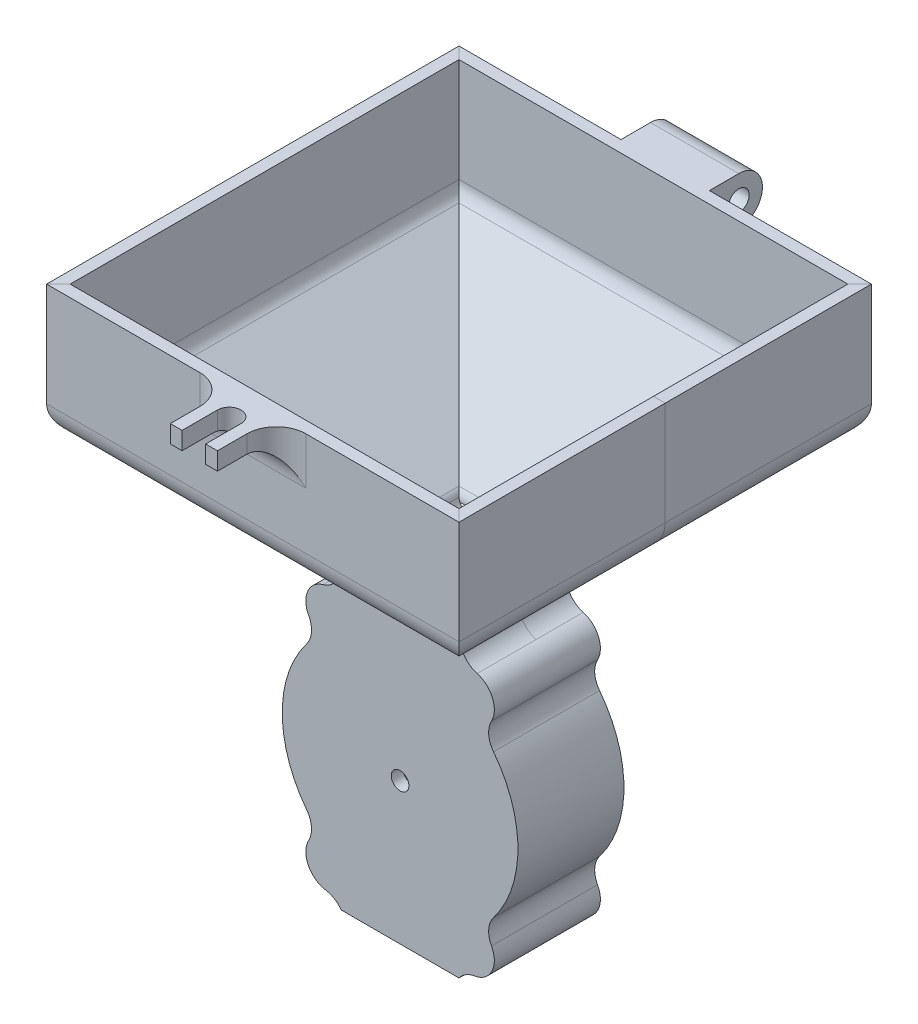
SolidWorks part; units mm, degrees
material "PP Copolymer"
ref_plane "Alzado" through (0, 0, 0) normal (0, 0, 1) x (1, 0, 0)
ref_plane "Planta" through (0, 0, 0) normal (0, 1, 0) x (1, 0, 0)
ref_plane "Vista lateral" through (0, 0, 0) normal (1, 0, 0) x (0, 0, -1)
sketch "Croquis1" plane through (0, 0, 0) normal (0, 0, 1) x (1, 0, 0)
  line L1 (0, 0) -> (0, 20) construction
  circle A0 centre (0, 0) radius 20
  dimension "D1" = 40
extrude "Saliente-Extruir1" add sketch "Croquis1" along normal mid plane 20
sketch "Croquis2" plane through (0, 0, 0) normal (0, 1, 0) x (1, 0, 0)
  line L1 (10, -10) -> (-10, -10)
  line L2 (10, -10) -> (10, 10)
  line L3 (10, 10) -> (-10, 10)
  line L4 (-10, -10) -> (-10, 10)
  line L5 (10, -10) -> (-10, 10) construction
  line L6 (10, 10) -> (-10, -10) construction
  dimension "D1" = 20
extrude "Saliente-Extruir2" add sketch "Croquis2" against normal blind 24
sketch "Croquis4" plane through (0, 0, 0) normal (0, 1, 0) x (1, 0, 0)
  line L1 (10, -10) -> (-10, -10)
  line L2 (10, -10) -> (10, 10)
  line L3 (10, 10) -> (-10, 10)
  line L4 (-10, -10) -> (-10, 10)
  line L5 (10, -10) -> (-10, 10) construction
  line L6 (10, 10) -> (-10, -10) construction
  line L7 (20, 10) -> (-20, 10) construction
  point P0 (0, 0)
extrude "Saliente-Extruir3" add sketch "Croquis4" along normal blind 28
shell "Vaciado1" thickness 2 removed face at (0, -24, 0) removed face at (0, 28, 0)
fillet "Redondeo1" radius 5 2 edges at (8, -16.1245, 0) (-8, -16.1245, 0)
sketch "Croquis6" plane through (0, 0, -10) normal (0, 0, -1) x (-1, 0, 0)
  line L6 (10, 17.3205) -> (10, 28)
  line L7 (10, 28) -> (-10, 28)
  line L8 (-10, 28) -> (-10, 17.3205)
  line L9 (10, 17.3205) -> (10, 28) construction
  line L10 (10, 28) -> (-10, 28) construction
  line L11 (-10, 28) -> (-10, 17.3205) construction
  line L12 (-10, -17.3205) -> (-10, -24)
  line L13 (-10, -17.3205) -> (-10, -24)
  line L14 (-10, -24) -> (10, -24)
  line L15 (-10, -24) -> (10, -24)
  line L16 (10, -24) -> (10, -17.3205)
  line L17 (10, -24) -> (10, -17.3205)
  arc A4 (10, -17.3205) -> (10, 17.3205) centre (0, 0) ccw
  arc A5 (-10, 17.3205) -> (-10, -17.3205) centre (0, 0) ccw
  arc A6 (10, -17.3205) -> (10, 17.3205) centre (0, 0) ccw construction
  arc A7 (-10, 17.3205) -> (-10, -17.3205) centre (0, 0) ccw construction
  dimension "D1" = 0
extrude "Cortar-Extruir2" cut sketch "Croquis6" against normal blind 2 contours A5 L6 L7 L8 A4 region at (0, 1.3583, -10)
sketch "Croquis7" plane through (0, 0, 8) normal (0, 0, -1) x (-1, 0, 0)
  line L0 (8, 28) -> (-0.2973, 19.7027)
  line L3 (8, 28) -> (-8, 28) construction
  line L4 (8, 28) -> (8, 16.1245)
  arc A0 (8, 16.1245) -> (0.3882, 17.9958) centre (0, 0) ccw
  arc A1 (-0.2973, 19.7027) -> (0.3882, 17.9958) centre (0.4098, 18.9956) ccw
  dimension "D3" = 2
  dimension "D2" = 45
extrude "Saliente-Extruir4" add sketch "Croquis7" along normal up to surface (16 mm away) up to face at (-11.1703, -0.9785, -8)
fillet "Redondeo2" radius 5 1 edges at (8, 16.1245, 0)
fillet "Redondeo3" radius 2 4 edges at (-10, 17.3205, 1) (-10, -17.3205, 1) (10, -17.3205, 1) (10, 17.3205, 1)
sketch "Croquis10" plane through (0, 0, 0) normal (0, 0, 1) x (1, 0, 0)
  line L0 (8, 28) -> (8, 28.9612)
  line L1 (8, 28.9612) -> (33, 48.9612)
  line L2 (10, 28) -> (35, 48)
  line L3 (8, 28) -> (10, 28) construction
  line L4 (35, 48) -> (35, 68)
  line L5 (33, 48.9612) -> (33, 68)
  line L6 (33, 68) -> (35, 68)
  line L7 (-8, 28) -> (8, 28) construction
  line L8 (8, 28) -> (10, 28)
  line L11 (0, 0) -> (0, 28) construction
  dimension "D1" = 2
  dimension "D2" = 20
  dimension "D3" = 40
  dimension "D4" = 35
  dimension "D5" = 38.66
sketch "Croquis11" plane through (0, 28, 0) normal (0, 1, 0) x (1, 0, 0)
  line L1 (-10, 10) -> (10, 10)
  line L2 (-10, 10) -> (-10, -10)
  line L3 (-10, -10) -> (10, -10)
  line L4 (10, 10) -> (10, -10)
  line L5 (-10, 10) -> (10, -10) construction
  line L6 (-10, -10) -> (10, 10) construction
  point P0 (0, 0)
sweep "Barrer2" add profiles "Croquis10" path "Croquis11"
fillet "Redondeo4" radius 2 5 edges at (8, 28.9612, -4) (0, 28.9612, -8) (8, 28.9612, 4) (-8, 28.9612, 0) (0, 28.9612, 8)
fillet "Redondeo5" radius 5 9 edges at (35, 48, 17.5) (10, 28, -4) (-35, 48, 0) (0, 48, -35) (0, 48, 35) (35, 48, -17.5) (10, 28, 5) (0, 28, 10) (-10, 28, 1)
fillet "Redondeo6" radius 3 6 edges at (33, 48.9612, 16.5) (0, 48.9612, -33) (-33, 48.9612, 0) (0, 48.9612, 33) (33, 48.9612, -16.5) (-8, 28, 0)
sketch "Croquis12" plane through (0, 0, 10) normal (0, 0, 1) x (1, 0, 0)
  circle A0 centre (0, 0) radius 1.5
  dimension "D1" = 3
extrude "Cortar-Extruir3" cut sketch "Croquis12" against normal blind 2
sketch "Croquis13" plane through (0, 68, 0) normal (0, 1, 0) x (1, 0, 0)
  line L0 (35, -35) -> (-35, -35) construction
  line L1 (4, -45) -> (2, -45)
  line L2 (4, -45) -> (4, -35)
  line L3 (4, -35) -> (-4, -35)
  line L4 (-4, -45) -> (-4, -35)
  line L5 (4, -45) -> (-4, -35) construction
  line L6 (4, -35) -> (-4, -45) construction
  line L7 (-2, -39) -> (-2, -45)
  line L8 (2, -39) -> (2, -45)
  line L9 (-2, -45) -> (-4, -45)
  arc A0 (2, -39) -> (-2, -39) centre (0, -39) ccw
  point P0 (0, -40)
  dimension "D3" = 2
  dimension "D1" = 10
  dimension "D2" = 8
  dimension "D4" = 1
extrude "Saliente-Extruir5" add sketch "Croquis13" against normal blind 3
fillet "Redondeo7" radius 5 2 edges at (-4, 66.5, 35) (4, 66.5, 35)
fillet "Redondeo8" radius 5 1 edges at (0, 65, 35)
sketch "Croquis14" plane through (0, 0, -8) normal (0, 0, -1) x (-1, 0, 0)
  line L0 (0, 0) -> (0, 28) construction
  line L1 (7.8385, 28) -> (-8, 28) construction
  line L4 (-10, -21.9032) -> (-10, -18.4391)
  line L5 (-10.9091, -16.7628) -> (-13.5192, -14.7388)
  line L6 (-10.9091, 16.7628) -> (-13.5192, 14.7388)
  line L7 (-10, 18.4391) -> (-10, 21.9032)
  line L10 (10, -21.9032) -> (10, -18.4391)
  line L19 (8, -18.9737) -> (8, -24)
  line L20 (8, -24) -> (10, -24)
  line L21 (10, -24) -> (10, -18.4391)
  line L22 (10, 18.4391) -> (10, 25.5969)
  line L23 (11.8765, 29.5012) -> (10, 28)
  line L24 (10, 28) -> (8, 28)
  line L25 (8, 28) -> (7.8385, 28)
  line L26 (7.3395, 27.3395) -> (-0.2973, 19.7027)
  line L29 (10, -21.9032) -> (10, -18.4391)
  line L30 (10, 18.4391) -> (10, 21.9032)
  circle A0 centre (-12, 18.4391) radius 2 construction
  arc A1 (-10, 21.9032) -> (-13.5192, 14.7388) centre (-12, 18.4391) ccw
  circle A2 centre (-12, -18.4391) radius 2 construction
  arc A3 (-13.5192, -14.7388) -> (-10, -21.9032) centre (-12, -18.4391) ccw
  arc A8 (-10.9091, 16.7628) -> (-10.9091, -16.7628) centre (0, 0) ccw construction
  circle A10 centre (12, -18.4391) radius 2 construction
  arc A11 (10, -21.9032) -> (13.5192, -14.7388) centre (12, -18.4391) ccw
  circle A13 centre (12, 18.4391) radius 2 construction
  arc A14 (13.5192, 14.7388) -> (10, 21.9032) centre (12, 18.4391) ccw
  arc A15 (10.9091, -16.7628) -> (10.9091, 16.7628) centre (0, 0) ccw construction
  arc A16 (10.9091, -16.7628) -> (13.5192, -14.7388) centre (0, 0) ccw
  arc A17 (13.5192, 14.7388) -> (10.9091, 16.7628) centre (0, 0) ccw
  arc A18 (-10.9091, -16.7628) -> (-10, -18.4391) centre (-12, -18.4391) cw
  arc A19 (10, -18.4391) -> (10.9091, -16.7628) centre (12, -18.4391) cw
  arc A20 (10, 18.4391) -> (10.9091, 16.7628) centre (12, 18.4391) ccw
  arc A21 (10.1739, -14.849) -> (0.3882, 17.9958) centre (0, 0) ccw
  arc A22 (10.1739, -14.849) -> (8, -18.9737) centre (13, -18.9737) ccw
  arc A23 (10.9091, -16.7628) -> (10, -18.4391) centre (12, -18.4391) ccw
  arc A24 (10.9091, -16.7628) -> (10.9091, 16.7628) centre (0, 0) ccw
  arc A25 (10, 18.4391) -> (10.9091, 16.7628) centre (12, 18.4391) ccw
  arc A26 (11.8765, 29.5012) -> (10, 25.5969) centre (15, 25.5969) ccw
  arc A27 (7.3395, 27.3395) -> (7.8385, 28) centre (5.2181, 29.4608) ccw
  arc A28 (-0.2973, 19.7027) -> (0.3882, 17.9958) centre (0.4098, 18.9956) ccw
  arc A31 (10.9091, -16.7628) -> (10, -18.4391) centre (12, -18.4391) ccw
  arc A32 (10.9091, -16.7628) -> (13.5192, -14.7388) centre (0, 0) ccw
  arc A33 (10, 18.4391) -> (10.9091, 16.7628) centre (12, 18.4391) ccw
  arc A34 (-10, 18.4391) -> (-10.9091, 16.7628) centre (-12, 18.4391) cw
  line M7 (-10, 25.5969) -> (-10, 18.4391)
  arc M9 (-10.9091, 16.7628) -> (-10.9091, -16.7628) centre (0, 0) ccw
  line M11 (-10, -18.4391) -> (-10, -24)
  line M12 (-10, -24) -> (-8, -24)
  dimension "D1" = 4
  dimension "D2" = 2
  dimension "D3" = 4
  dimension "D5" = 4
  dimension "D4" = 2
  dimension "D6" = 2
  dimension "D8" = 2
  dimension "D7" = 0
extrude "Saliente-Extruir6" add sketch "Croquis14" against normal blind 18 contours A17 A14 L30 A13 | A16 A10 L10 A11 | A3 A2 M9 M12 M11 | A1 A0 M7 M9 region at (12.9136, -18.9006, -8) region at (12.9136, 18.9006, -8) region at (-12.9136, -18.9006, -8) region at (-12.9136, 18.9006, -8)
sketch "Croquis15" plane through (0, 0, -8) normal (0, 0, -1) x (-1, 0, 0)
  circle A0 centre (-12, 18.4391) radius 2
  circle A1 centre (12, 18.4391) radius 2
  circle A2 centre (12, -18.4391) radius 2
  circle A3 centre (-12, -18.4391) radius 2
  dimension "D1" = 4
extrude "Cortar-Extruir4" cut sketch "Croquis15" against normal blind 10
fillet "Redondeo9" radius 4 6 edges at (-13.5192, -14.7388, 1) (13.5192, -14.7388, 1) (13.5192, 14.7388, 1) (10, 21.9032, 1) (-10, 21.9032, 1) (-13.5192, 14.7388, 1)
fillet "Redondeo10" radius 4 2 edges at (10, -21.9032, 1) (-10, -21.9032, 1)
sketch "Croquis17" plane through (0, 0, 0) normal (1, 0, 0) x (0, 0, -1)
  line L1 (40, 60) -> (35, 60)
  line L3 (40, 68) -> (35, 68)
  line L4 (35, 60) -> (35, 68)
  circle A0 centre (40, 64) radius 1.75
  arc A1 (40, 60) -> (40, 68) centre (40, 64) ccw
  dimension "D1" = 8
  dimension "D2" = 3.5
  dimension "D3" = 5
extrude "Saliente-Extruir7" add sketch "Croquis17" along normal mid plane 15
